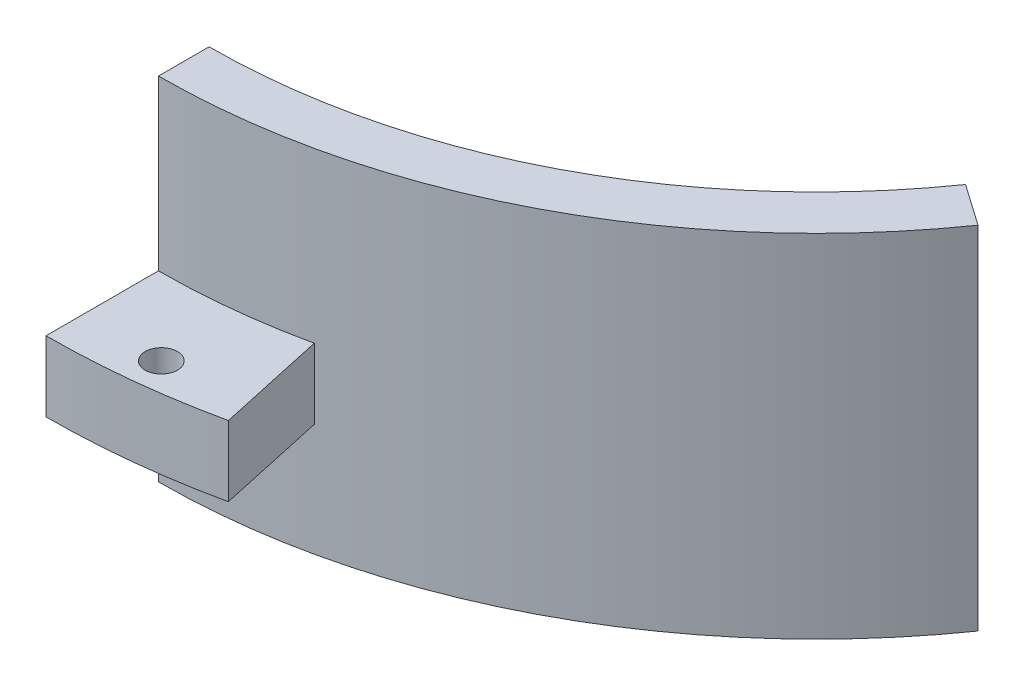
SolidWorks part; units mm, degrees
ref_plane "Front Plane" through (0, 0, 0) normal (0, 0, 1) x (1, 0, 0)
ref_plane "Top Plane" through (0, 0, 0) normal (0, 1, 0) x (1, 0, 0)
ref_plane "Right Plane" through (0, 0, 0) normal (1, 0, 0) x (0, 0, -1)
sketch "Sketch2" plane through (0, 0, 0) normal (0, 1, 0) x (1, 0, 0)
  line L0 (0, -46.8) -> (0, -43.2)
  line L1 (38.3363, -26.8434) -> (35.3874, -24.7785)
  line L2 (0, 0) -> (35.3874, -24.7785) construction
  circle A0 centre (0, 0) radius 46.8
  circle A1 centre (0, 0) radius 43.2
  dimension "D1" = 93.6
  dimension "D3" = 55
  dimension "D2" = 3.6
extrude "Boss-Extrude1" add sketch "Sketch2" along normal blind 25 contours A1 L0 A0 L1 region at (20.0007, 0, 38.421)
sketch "Sketch3" plane through (0, 25, 0) normal (0, 1, 0) x (1, 0, 0)
  line L0 (0, -43.2) -> (0, -40)
  line L1 (35.3874, -24.7785) -> (32.7661, -22.9431)
  line L2 (38.3363, -26.8434) -> (35.3874, -24.7785) construction
  circle A0 centre (0, 0) radius 40
  circle A2 centre (0, 0) radius 44.8
  arc M6 (35.3874, -24.7785) -> (0, -43.2) centre (0, 0) cw
  dimension "D1" = 80
  dimension "D2" = 89.6
extrude "Boss-Extrude2" add sketch "Sketch3" against normal blind 13 from offset 6 contours A0 L0 L1 M6 region at (18.4888, 25, 35.5166) offset against normal yes
sketch "Sketch4" plane through (0, 25, 0) normal (0, 1, 0) x (1, 0, 0)
  line L0 (0, -46.8) -> (0, -54.8)
  line L1 (10, -45.7191) -> (11.7094, -53.5344)
  line L2 (0, 0) -> (10, -45.7191) construction
  circle A0 centre (0, 0) radius 54.8
  arc A2 (0, -46.8) -> (38.3363, -26.8434) centre (0, 0) ccw construction
  circle A3 centre (0, 0) radius 46.8
  arc M7 (0, -46.8) -> (38.3363, -26.8434) centre (0, 0) ccw
  dimension "D1" = 8
  dimension "D2" = 10
extrude "Boss-Extrude3" add sketch "Sketch4" against normal blind 5 from offset 12 contours L0 A0 L1 M7 region at (5.4597, 25, 50.5125) offset against normal yes
sketch "Sketch5" plane through (0, 13, 0) normal (0, 1, 0) x (1, 0, 0)
  line L0 (5.0291, -46.529) -> (5.8888, -54.4827) construction
  circle A0 centre (5.647, -52.2457) radius 1.15
  arc A1 (0, -46.8) -> (10, -45.7191) centre (0, 0) ccw construction
  arc A2 (0, -54.8) -> (11.7094, -53.5344) centre (0, 0) ccw construction
  dimension "D1" = 2.3
  dimension "D2" = 2.25
extrude "M2 holes" cut sketch "Sketch5" against normal up to next
sketch "Sketch6" plane through (0, 19, 0) normal (0, 1, 0) x (1, 0, 0)
  line L0 (0, -40) -> (0, -43)
  line L1 (0, -43.2) -> (0, -40) construction
  line L2 (0, -43) -> (5, -39.6863)
  arc A0 (0, -40) -> (32.7661, -22.9431) centre (0, 0) ccw construction
  arc A1 (0, -40) -> (5, -39.6863) centre (0, 0) ccw
  dimension "D1" = 3
  dimension "D2" = 5
extrude "Cut-Extrude1" cut sketch "Sketch6" against normal up to next
